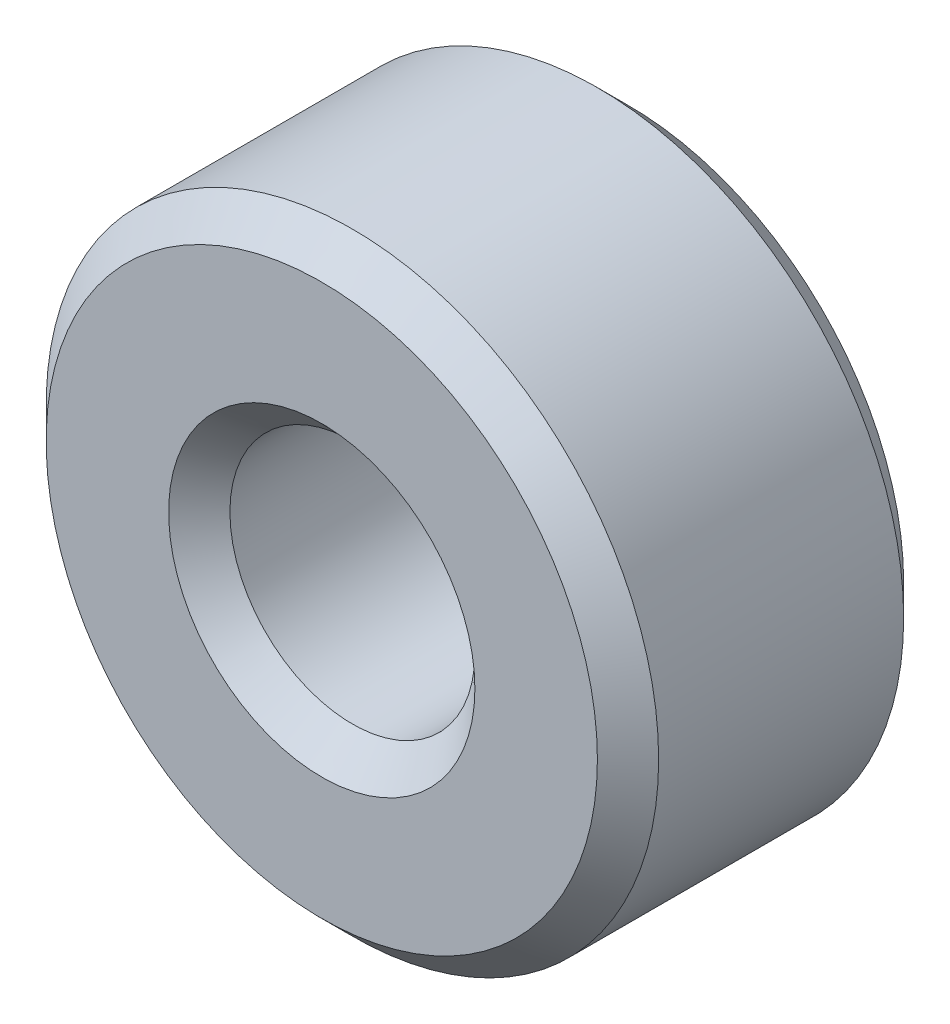
SolidWorks part; units mm, degrees
ref_plane "Front Plane" through (0, 0, 0) normal (0, 0, 1) x (1, 0, 0)
ref_plane "Top Plane" through (0, 0, 0) normal (0, 1, 0) x (1, 0, 0)
ref_plane "Right Plane" through (0, 0, 0) normal (1, 0, 0) x (0, 0, -1)
sketch "Sketch1" plane through (0, 0, 0) normal (0, 0, 1) x (1, 0, 0)
  circle A0 centre (-28.1958, 6.261) radius 4
  circle A1 centre (-28.1958, 6.261) radius 10
  dimension "D1" = 8
  dimension "D2" = 20
extrude "Boss-Extrude1" add sketch "Sketch1" along normal blind 10
chamfer "Chamfer1" distance 1 angle 45 4 edges at (-18.1958, 6.261, 0) (-18.1958, 6.261, 10) (-24.1958, 6.261, 0) (-24.1958, 6.261, 10)
